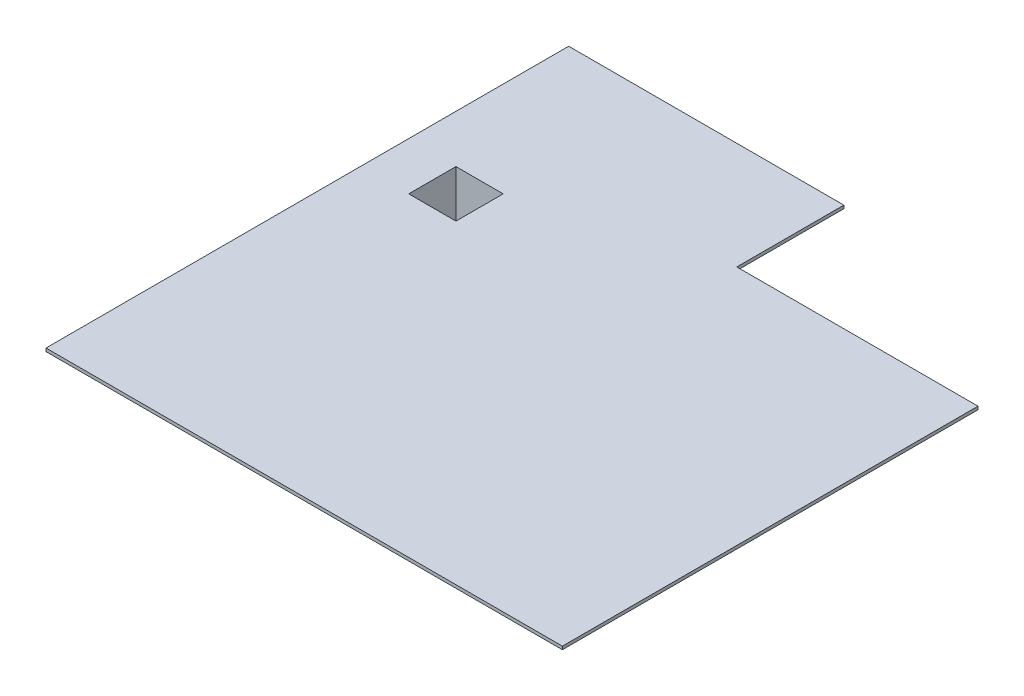
SolidWorks part; units mm, degrees
ref_plane "Спереди" through (0, 0, 0) normal (0, 0, 1) x (1, 0, 0)
ref_plane "Сверху" through (0, 0, 0) normal (0, 1, 0) x (1, 0, 0)
ref_plane "Справа" through (0, 0, 0) normal (1, 0, 0) x (0, 0, -1)
sketch "Эскиз1" plane through (0, 0, 0) normal (0, 1, 0) x (1, 0, 0)
  line L0 (16400, 13200) -> (8740, 13200)
  line L1 (0, 0) -> (16400, 0)
  line L2 (0, 0) -> (0, 16600)
  line L3 (8740, 13200) -> (8740, 16600)
  line L4 (16400, 0) -> (16400, 13200)
  line L5 (8740, 16600) -> (0, 16600)
  dimension "D1" = 16400
  dimension "D2" = 13200
  dimension "D3" = 7660
  dimension "D4" = 16600
extrude "Вытянуть1" add sketch "Эскиз1" along normal blind 100
sketch "Эскиз5" plane through (0, 100, 0) normal (0, 1, 0) x (1, 0, 0)
  line L0 (16400, 0) -> (16400, 13200) construction
  line L1 (1520, 11500) -> (3020, 11500)
  line L2 (1520, 11500) -> (1520, 10000)
  line L3 (1520, 10000) -> (3020, 10000)
  line L4 (3020, 11500) -> (3020, 10000)
  line L5 (0, 0) -> (16400, 0) construction
  dimension "D1" = 13380
  dimension "D2" = 10000
extrude "Вытянуть-Тонкостенный3" add sketch "Эскиз5" against normal blind 2200 thin thin type one direction wall 100
extrude "Вытянуть3" cut sketch "Эскиз5<3>" against normal blind 2200
sketch "Эскиз5<3>" plane through (0, 100, 0) normal (0, 1, 0) x (1, 0, 0) same geometry as "Эскиз5"
